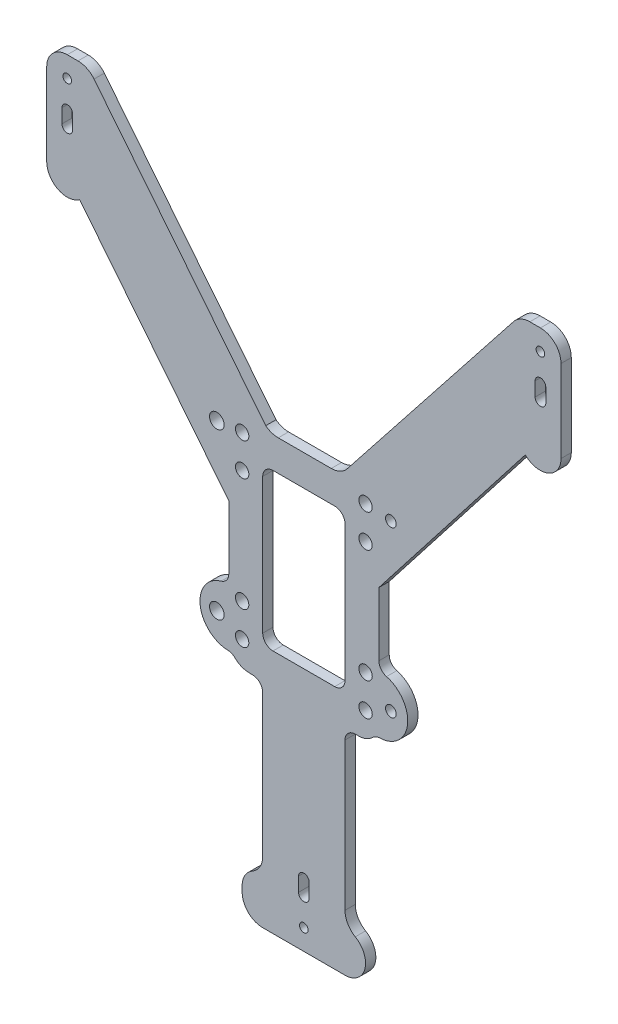
SolidWorks part; units mm, degrees
ref_plane "Front Plane" through (0, 0, 0) normal (0, 0, 1) x (1, 0, 0)
ref_plane "Top Plane" through (0, 0, 0) normal (0, 1, 0) x (1, 0, 0)
ref_plane "Right Plane" through (0, 0, 0) normal (1, 0, 0) x (0, 0, -1)
ref_plane "Plane1" through (0, 0, 5) normal (0, 0, 1) x (1, 0, 0)
sketch "Sketch7" plane through (0, 0, 5) normal (0, 0, 1) x (1, 0, 0)
  line L0 (-30, -147.3205) -> (-30, -150)
  line L1 (-20, -160) -> (20, -160)
  line L2 (20, -132.6795) -> (20, -61)
  line L3 (25, -56) -> (26.5, -56)
  line L4 (36.5, -19.3636) -> (36.5, 11.4955)
  line L5 (36.5, 11.4955) -> (107.6557, 102.8973)
  line L6 (125, 110) -> (125, 150)
  line L7 (115, 160) -> (109.8448, 160)
  line L8 (101.9972, 156.198) -> (20.6377, 53.1837)
  line L9 (13.3207, 50) -> (-12.443, 50)
  line L10 (-18.5322, 52.0677) -> (-101.9976, 156.2523)
  line L11 (-109.802, 160) -> (-115, 160)
  line L12 (-125, 150) -> (-125, 110)
  line L13 (-109.0014, 101.9989) -> (-36.5, 11.5)
  line L14 (-36.5, 11.5) -> (-36.5, -19.3636)
  line L15 (-26.5, -56) -> (-25, -56)
  line L16 (-20, -61) -> (-20, -130)
  line L17 (117.6, 136.4) -> (117.6, 129.6)
  line L18 (112.4, 129.6) -> (112.4, 136.4)
  line L19 (-112.4, 136.4) -> (-112.4, 129.6)
  line L20 (-117.6, 129.6) -> (-117.6, 136.4)
  line L21 (2.6, -129.6) -> (2.6, -136.4)
  line L22 (-2.6, -136.4) -> (-2.6, -129.6)
  line L23 (-20, -36) -> (-20, 30)
  line L24 (-15, 35) -> (15, 35)
  line L25 (20, 30) -> (20, -36)
  line L26 (15, -41) -> (-15, -41)
  arc A0 (-30, -150) -> (-20, -160) centre (-20, -150) ccw
  arc A1 (20, -160) -> (25, -141.3397) centre (20, -150) ccw
  arc A2 (25, -141.3397) -> (20, -132.6795) centre (30, -132.6795) cw
  arc A3 (20, -61) -> (25, -56) centre (25, -61) cw
  arc A4 (26.5, -56) -> (33.5173, -53.1244) centre (26.5, -46) ccw
  arc A5 (33.5173, -53.1244) -> (36.8876, -51.6885) centre (37.026, -56.6866) cw
  arc A6 (36.8876, -51.6885) -> (40.1842, -24.1874) centre (36.5, -37.6939) ccw
  arc A7 (40.1842, -24.1874) -> (36.5, -19.3636) centre (41.5, -19.3636) cw
  arc A8 (107.6557, 102.8973) -> (115, 100) centre (114.6996, 109.9955) ccw
  arc A9 (115, 100) -> (125, 110) centre (115, 110) ccw
  arc A10 (125, 150) -> (115, 160) centre (115, 150) ccw
  arc A11 (109.8448, 160) -> (101.9972, 156.198) centre (109.8448, 150) ccw
  arc A12 (20.6377, 53.1837) -> (13.3207, 50) centre (13.3207, 60) cw
  arc A13 (-12.443, 50) -> (-18.5322, 52.0677) centre (-12.443, 60) cw
  arc A14 (-101.9976, 156.2523) -> (-109.802, 160) centre (-109.802, 150) ccw
  arc A15 (-115, 160) -> (-125, 150) centre (-115, 150) ccw
  arc A16 (-125, 110) -> (-109.0014, 101.9989) centre (-115, 110) ccw
  arc A17 (-36.5, -19.3636) -> (-40.1842, -24.1874) centre (-41.5, -19.3636) cw
  arc A18 (-40.1842, -24.1874) -> (-36.8876, -51.6885) centre (-36.5, -37.6939) ccw
  arc A19 (-36.8876, -51.6885) -> (-33.5173, -53.1244) centre (-37.026, -56.6866) cw
  arc A20 (-33.5173, -53.1244) -> (-26.5, -56) centre (-26.5, -46) ccw
  arc A21 (-25, -56) -> (-20, -61) centre (-25, -61) cw
  arc A22 (-20, -130) -> (-25, -138.6603) centre (-30, -130) cw
  arc A23 (-25, -138.6603) -> (-30, -147.3205) centre (-20, -147.3205) ccw
  arc A24 (112.4, 136.4) -> (117.6, 136.4) centre (115, 136.4) cw
  arc A25 (117.6, 129.6) -> (112.4, 129.6) centre (115, 129.6) cw
  arc A26 (-117.6, 136.4) -> (-112.4, 136.4) centre (-115, 136.4) cw
  arc A27 (-112.4, 129.6) -> (-117.6, 129.6) centre (-115, 129.6) cw
  arc A28 (-2.6, -129.6) -> (2.6, -129.6) centre (0, -129.6) cw
  arc A29 (2.6, -136.4) -> (-2.6, -136.4) centre (0, -136.4) cw
  arc A30 (-15, -41) -> (-20, -36) centre (-15, -36) cw
  arc A31 (-20, 30) -> (-15, 35) centre (-15, 30) cw
  arc A32 (15, 35) -> (20, 30) centre (15, 30) cw
  arc A33 (20, -36) -> (15, -41) centre (15, -36) cw
base flange "Base-Flange1" sketch "Sketch7" thickness 5 reverse thickness direction yes parameters "D1"=0
hole_wizard "Ø5.2 (5.2) Diameter Hole1" positions "Sketch11" profile "Sketch10" hole size "Ø5.2" standard "ANSI Metric"
sketch "Sketch11" plane through (0, 0, 5) normal (0, 0, 1) x (1, 0, 0)
  point P0 (42.3, -37.6939)
  point P1 (42.3, 42.3061)
sketch "Sketch10" plane through (42.3, -37.6939, 5) normal (1, 0, 0) x (0, -1, 0)
  line L0 (0, 0) -> (0, 5)
  line L1 (0, 5) -> (2.6, 5)
  line L2 (2.6, 5) -> (2.6, 0)
  line L5 (2.6, 0) -> (0, 0)
  line L11 (0, -6.35) -> (0, 107.95) construction
  dimension "Thru Hole Dia." = 5.2
  dimension "Thru Hole Depth" = 5
hole_wizard "Ø7.1 (7.1) Diameter Hole1" positions "Sketch13" profile "Sketch12" hole size "Ø7.1" standard "ANSI Metric"
sketch "Sketch13" plane through (0, 0, 5) normal (0, 0, 1) x (1, 0, 0)
  point P0 (-42.3, -37.6939)
  point P1 (-42.3, 42.3061)
sketch "Sketch12" plane through (-42.3, -37.6939, 5) normal (1, 0, 0) x (0, -1, 0)
  line L0 (0, 0) -> (0, 5)
  line L1 (0, 5) -> (3.55, 5)
  line L2 (3.55, 5) -> (3.55, 0)
  line L5 (3.55, 0) -> (0, 0)
  line L11 (0, -6.35) -> (0, 107.95) construction
  dimension "Thru Hole Dia." = 7.1
  dimension "Thru Hole Depth" = 5
hole_wizard "Ø6.5 (6.5) Diameter Hole1" positions "Sketch15" profile "Sketch14" hole size "Ø6.5" standard "ANSI Metric"
sketch "Sketch15" plane through (0, 0, 5) normal (0, 0, 1) x (1, 0, 0)
  point P0 (-30, -43.5)
  point P1 (-30, 43.5)
  point P2 (-30, -27.5)
  point P3 (-30, 27.5)
  point P4 (30, -43.5)
  point P5 (30, -27.5)
  point P6 (30, 27.5)
  point P7 (30, 43.5)
sketch "Sketch14" plane through (-30, -43.5, 5) normal (1, 0, 0) x (0, -1, 0)
  line L0 (0, 0) -> (0, 5)
  line L1 (0, 5) -> (3.25, 5)
  line L2 (3.25, 5) -> (3.25, 0)
  line L5 (3.25, 0) -> (0, 0)
  line L11 (0, -6.35) -> (0, 107.95) construction
  dimension "Thru Hole Dia." = 6.5
  dimension "Thru Hole Depth" = 5
hole_wizard "Ø4.2 (4.2) Diameter Hole1" positions "Sketch17" profile "Sketch16" hole size "Ø4.2" standard "ANSI Metric"
sketch "Sketch17" plane through (0, 0, 5) normal (0, 0, 1) x (1, 0, 0)
  point P0 (0, -150)
  point P1 (-115, 150)
  point P2 (115, 150)
sketch "Sketch16" plane through (0, -150, 5) normal (1, 0, 0) x (0, -1, 0)
  line L0 (0, 0) -> (0, 5)
  line L1 (0, 5) -> (2.1, 5)
  line L2 (2.1, 5) -> (2.1, 0)
  line L5 (2.1, 0) -> (0, 0)
  line L11 (0, -6.35) -> (0, 107.95) construction
  dimension "Thru Hole Dia." = 4.2
  dimension "Thru Hole Depth" = 5
ref_point "Point1"
ref_point "Point2"
ref_point "Point3"
ref_point "Point4"
ref_point "Point5"
ref_point "Point7"
sketch "Sketch19" plane through (0, 0, 5) normal (0, 0, 1) x (1, 0, 0)
  line L0 (-115, 136.4) -> (-115, 129.6) construction
  line L1 (-117.6, 133) -> (-112.4, 133) construction
  line L2 (-117.6, 136.4) -> (-117.6, 129.6) construction
  line L3 (-112.4, 129.6) -> (-112.4, 136.4) construction
  line L4 (115, 136.4) -> (115, 129.6) construction
  line L5 (117.6, 133) -> (112.4, 133) construction
  line L6 (117.6, 129.6) -> (117.6, 136.4) construction
  line L7 (112.4, 136.4) -> (112.4, 129.6) construction
  line L8 (0, -129.6) -> (0, -136.4) construction
  line L9 (-2.6, -133) -> (2.6, -133) construction
  line L10 (-2.6, -129.6) -> (-2.6, -136.4) construction
  line L11 (2.6, -136.4) -> (2.6, -129.6) construction
  point P10 (-115, 133)
  point P11 (115, 136.4)
  point P33 (0, -133)
  point P34 (115, 133)
ref_plane "Plane2" through (0, 0, 0) normal (1, 0, 0) x (0, 0, -1)
sketch "Bend-Lines1" plane through (0, 0, 0) normal (0, 1, 0) x (1, 0, 0)
sketch "Bounding-Box1" plane through (0, 0, 0) normal (0, 1, 0) x (1, 0, 0)
sheet metal parameters "Sheet-Metal(5)" thickness 5 parameters "D1"=0
flat pattern "Flat-Pattern(5)" [suppressed]
sketch "Bend-Lines3" plane through (0, 0, 0) normal (0, 1, 0) x (1, 0, 0)
sketch "Bounding-Box3" [suppressed] plane through (0, 0, 0) normal (0, 1, 0) x (1, 0, 0)
sheet metal parameters "Sheet-Metal(6)" thickness 5 parameters "D1"=0
flat pattern "Flat-Pattern(5)"
sketch "Bend-Lines3" plane through (0, 0, 0) normal (0, 1, 0) x (1, 0, 0)
sketch "Bounding-Box3" [suppressed] plane through (0, 0, 0) normal (0, 1, 0) x (1, 0, 0)
sheet metal parameters "Sheet-Metal(7)" thickness 5 parameters "D1"=0
flat pattern "Flat-Pattern(5)"
sketch "Bend-Lines3" plane through (0, 0, 0) normal (0, 1, 0) x (1, 0, 0)
sketch "Bounding-Box3" [suppressed] plane through (0, 0, 0) normal (0, 1, 0) x (1, 0, 0)
sheet metal parameters "Sheet-Metal(8)" thickness 5 parameters "D1"=0
flat pattern "Flat-Pattern(5)"
sketch "Bend-Lines3" plane through (0, 0, 0) normal (0, 1, 0) x (1, 0, 0)
sketch "Bounding-Box3" [suppressed] plane through (0, 0, 0) normal (0, 1, 0) x (1, 0, 0)
sheet metal parameters "Sheet-Metal(9)" thickness 5 parameters "D1"=0
flat pattern "Flat-Pattern(5)"
sketch "Bend-Lines3" plane through (0, 0, 0) normal (0, 1, 0) x (1, 0, 0)
sketch "Bounding-Box3" [suppressed] plane through (0, 0, 0) normal (0, 1, 0) x (1, 0, 0)
